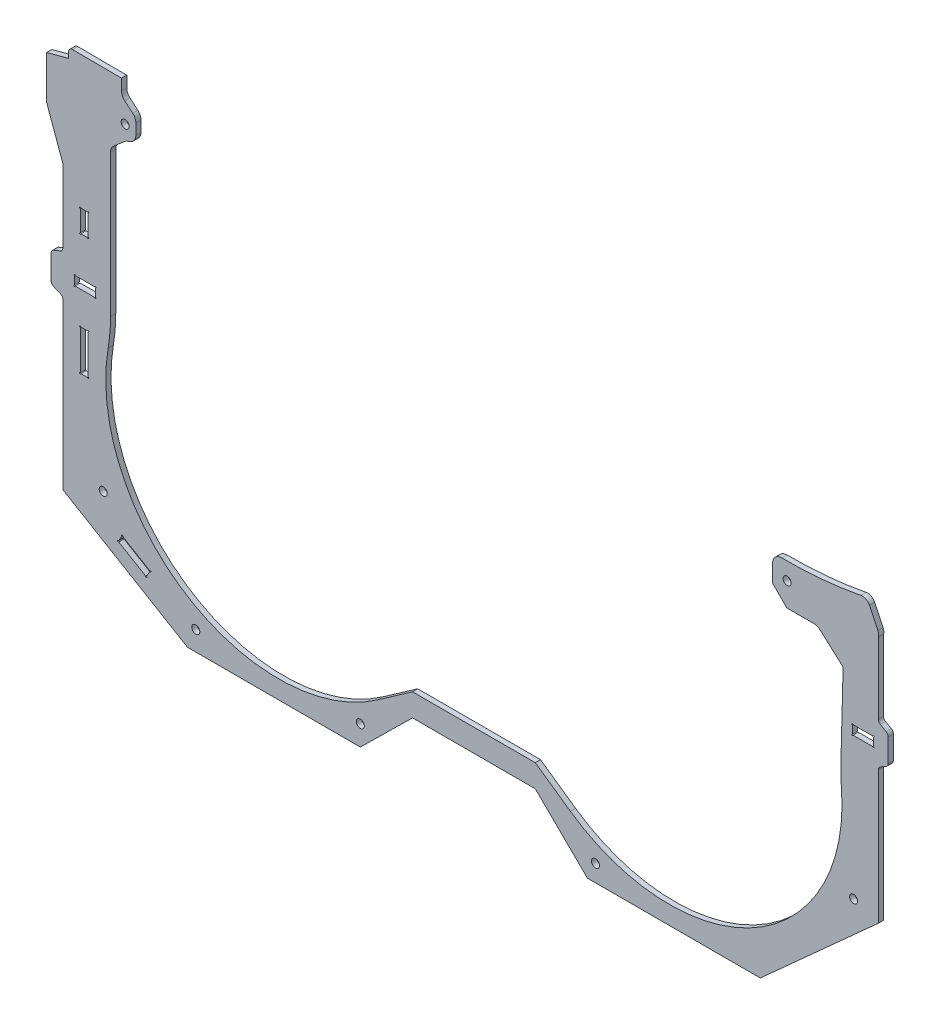
SolidWorks part; units mm, degrees
material "PPS"
ref_plane "前视基准面" through (0, 0, 0) normal (0, 0, 1) x (1, 0, 0)
ref_plane "上视基准面" through (0, 0, 0) normal (0, 1, 0) x (1, 0, 0)
ref_plane "右视基准面" through (0, 0, 0) normal (1, 0, 0) x (0, 0, -1)
sketch "草图1" plane through (0, 0, 0) normal (0, 0, 1) x (1, 0, 0)
  line L0 (-816.4831, 0) -> (39952.7477, 0) construction
  line L1 (0, 10.8762) -> (0, -592.6628) construction
  line L2 (0, 0) -> (206.9686, -284.8678) construction
  line L9 (155.1848, -135.6229) -> (109.8918, -176.4655)
  line L10 (109.8918, -176.4655) -> (43.5772, -176.4655)
  line L60 (-109.8918, -176.4655) -> (-43.5772, -176.4655)
  line L119 (-133.4625, -19.9819) -> (-139.4195, -25.1039)
  line L187 (152.75, -77.5) -> (145.75, -77.5) construction
  line L188 (152.75, -77.5) -> (152.75, -75) construction
  line L189 (145.75, -77.5) -> (145.75, -75) construction
  line L190 (152.75, -75) -> (145.75, -75) construction
  line L191 (-145.75, -75) -> (-152.75, -75) construction
  line L192 (-152.75, -75) -> (-152.75, -77.5) construction
  line L193 (-152.75, -77.5) -> (-145.75, -77.5) construction
  line L194 (-145.75, -77.5) -> (-145.75, -75) construction
  line L195 (145.25, -74.5) -> (153.25, -74.5)
  line L196 (153.25, -74.5) -> (153.25, -78)
  line L197 (153.25, -78) -> (145.25, -78)
  line L198 (145.25, -78) -> (145.25, -74.5)
  line L199 (-153.25, -78) -> (-145.25, -78)
  line L200 (-153.25, -74.5) -> (-153.25, -78)
  line L201 (-145.25, -74.5) -> (-153.25, -74.5)
  line L202 (-145.25, -78) -> (-145.25, -74.5)
  line L204 (-135.1929, 0) -> (-155.5041, 0.108)
  line L205 (-155.5041, 3.8169) -> (-155.5041, -3.6009) construction
  line L206 (-155.5041, 0.108) -> (-155.5041, -3.6009)
  line L207 (-155.5041, -3.6009) -> (-163.9299, -5.8429)
  line L208 (-155.5041, -3.6009) -> (-170.0041, -7.4592) construction
  line L209 (-163.9299, -5.8429) -> (-163.9299, -22.4613)
  line L210 (-163.9299, -22.4613) -> (-157.7253, -39.5836)
  line L211 (-157.7253, -39.5836) -> (-157.7253, -148.0115)
  line L212 (-157.7253, -148.0115) -> (-109.8918, -176.4655)
  line L215 (114.5778, -32.685) -> (114.5778, -42.9165)
  line L216 (120.0778, -48.4165) -> (131.782, -48.4165)
  line L217 (131.782, -48.4165) -> (141.6604, -57.2625)
  line L219 (151.7709, -31.6811) -> (155.0114, -38.4796)
  line L220 (155.1848, -40.6053) -> (155.1848, -135.6229)
  line L221 (120.1823, -39.335) -> (149.4323, -39.335) construction
  line L222 (91.0014, -48.4165) -> (142.5788, -48.4165) construction
  line L223 (75, -103.2286) -> (164.6276, -103.2286) construction
  line L224 (75, -103.2286) -> (37.0006, -157.4975) construction
  line L226 (37.0006, -157.4975) -> (23.5599, -148.0862)
  line L227 (23.5599, -148.0862) -> (-23.5599, -148.0862)
  line L228 (23.5599, -156.7643) -> (-23.5599, -156.7643)
  line L229 (23.5599, -156.7643) -> (43.5772, -176.4655)
  line L230 (-37.0006, -157.4975) -> (-23.5599, -148.0862)
  line L231 (-23.5599, -156.7643) -> (-43.5772, -176.4655)
  line L233 (114.5778, -42.9165) -> (120.0778, -48.4165)
  line L234 (75, -103.2286) -> (140.6832, -94.5813) construction
  line L235 (141.6604, -57.2625) -> (140.6832, -94.5813)
  line L236 (140.6832, -94.5813) -> (140.6832, -61.0285) construction
  line L238 (-139.4195, -87.7629) -> (-75, -103.2286) construction
  line L239 (-75, -103.2286) -> (-141.25, -103.2286) construction
  line L240 (-139.4195, -25.1039) -> (-139.4195, -87.7629)
  line L241 (-135.1929, 0) -> (-135.1929, -5.85)
  line L242 (-135.1929, -5.85) -> (-129.7197, -10.5767)
  line L243 (-129.7197, -10.5767) -> (-129.7197, -18.7984)
  line L244 (-129.7197, -18.7984) -> (-133.4625, -19.9819)
  circle A76 centre (75, -103.2286) radius 66.25 construction
  circle A78 centre (-133.8062, -14.6009) radius 1.55
  arc A79 (155.0114, -38.4796) -> (155.1848, -40.6053) centre (152.3033, -39.7704) cw
  circle A80 centre (-75, -103.2286) radius 66.25 construction
  arc A81 (148.5011, -30.0249) -> (151.7709, -31.6811) centre (149.0628, -32.9719) cw
  arc A82 (153.902, -42.309) -> (155.0114, -38.4796) centre (152.3033, -39.7704) ccw construction
  arc A83 (148.5011, -30.0249) -> (114.5778, -32.685) centre (119.5082, 122.0773) cw
  arc A84 (97.7907, -31.2329) -> (148.5011, -30.0249) centre (119.5082, 122.0773) ccw construction
  circle A85 centre (149.4323, -39.335) radius 1.55 construction
  circle A86 centre (120.1823, -39.335) radius 1.55
  arc A87 (37.0006, -157.4975) -> (141.25, -103.2286) centre (75, -103.2286) ccw
  arc A88 (-37.0006, -157.4975) -> (-141.25, -103.2286) centre (-75, -103.2286) cw
  arc A89 (140.6832, -94.5813) -> (141.25, -103.2286) centre (75, -103.2286) cw
  arc A91 (-141.25, -103.2286) -> (-139.4195, -87.7629) centre (-75, -103.2286) cw
  point P10 (149.25, -75)
  point P29 (0, -148.0862)
  point P38 (153.25, -76.25)
  point P92 (0, -156.7643)
  dimension "D1" = 36
  dimension "D2" = 75
  dimension "D3" = 132.5
  dimension "D6" = 75
  dimension "D7" = 149.25
  dimension "D15" = 125
  dimension "D14" = 3.1
  dimension "D4" = 2.5
  dimension "D5" = 7
  dimension "D8" = 7
  dimension "D9" = 0.5
  dimension "D10" = 0.5
  dimension "D11" = 0.5
  dimension "D12" = 0.5
  dimension "D13" = 29.25
  dimension "D16" = 7.5
  dimension "D17" = 1.5
  dimension "D18" = 13.5
extrude "凸台-拉伸1" add sketch "草图1" along normal blind 2
sketch "草图2" plane through (0, 0, 0) normal (0, 0, 1) x (1, 0, 0)
  line L0 (155.1848, -68.75) -> (158.9348, -70.9151)
  line L1 (155.1848, -135.6229) -> (155.1848, -40.6053) construction
  line L2 (158.9348, -70.9151) -> (158.9348, -81.5849)
  line L3 (158.9348, -81.5849) -> (155.1848, -83.75)
  line L4 (155.1848, -83.75) -> (155.1848, -68.75)
  line L5 (153.25, -76.25) -> (184.2947, -76.25) construction
  line L6 (153.25, -78) -> (153.25, -74.5) construction
  line L7 (-153.25, -76.25) -> (-171.2105, -76.25) construction
  line L8 (-153.25, -74.5) -> (-153.25, -78) construction
  line L9 (-157.7253, -68.75) -> (-157.7253, -83.75)
  line L10 (-157.7253, -39.5836) -> (-157.7253, -148.0115) construction
  line L11 (-157.7253, -83.75) -> (-162.2253, -81.886)
  line L12 (-162.2253, -81.886) -> (-162.2253, -70.614)
  line L13 (-162.2253, -70.614) -> (-157.7253, -68.75)
  dimension "D1" = 3.75
  dimension "D2" = 7.5
  dimension "D3" = 60
  dimension "D4" = 67.5
  dimension "D5" = 4.5
extrude "凸台-拉伸2" add sketch "草图2" against normal up to surface from surface up to face at (-132.2562, -14.6009, 0) starting at face at (149.25, -76.25, 2)
fillet "圆角1" radius 66.25 2 edges at (-139.4195, -87.7629, 1) (140.6832, -94.5813, 1)
fillet "圆角4" radius 1.5 9 edges at (155.1848, -68.75, 1) (158.9348, -70.9151, 1) (155.1848, -83.75, 1) (158.9348, -81.5849, 1) (-155.5041, 0.108, 1) (-157.7253, -68.75, 1) (-162.2253, -70.614, 1) (-162.2253, -81.886, 1) (-157.7253, -83.75, 1)
sketch "板状设备接口" plane through (0, 0, 2) normal (0, 0, 1) x (1, 0, 0)
  line L0 (-151, -90.5) -> (-148, -90.5)
  line L1 (-148, -90.5) -> (-148, -106)
  line L2 (-148, -106) -> (-151, -106)
  line L3 (-151, -106) -> (-151, -90.5)
  line L4 (-148, -77.5) -> (-148, -75) construction
  line L5 (-151, -75) -> (-151, -77.5) construction
  line L6 (-151, -51) -> (-148, -51)
  line L7 (-148, -51) -> (-148, -59.5)
  line L8 (-148, -59.5) -> (-151, -59.5)
  line L9 (-151, -59.5) -> (-151, -51)
  line L10 (-145.25, -74.5) -> (-153.25, -74.5) construction
  line L11 (-153.25, -78) -> (-145.25, -78) construction
  line L12 (-134.9623, -151.9529) -> (-124.2193, -158.3434)
  line L13 (-124.2193, -158.3434) -> (-125.753, -160.9217)
  line L14 (-125.753, -160.9217) -> (-136.496, -154.5312)
  line L15 (-136.496, -154.5312) -> (-134.9623, -151.9529)
  line L21 (-157.7253, -148.0115) -> (-109.8918, -176.4655) construction
  line L22 (-131.1245, -157.7265) -> (-133.8085, -162.2385) construction
  dimension "D1" = 15
  dimension "D2" = 8.5
  dimension "D3" = 12.5
  dimension "D4" = 15.5
  dimension "D5" = 5.25
  dimension "D6" = 12.5
  dimension "D7" = 3
extrude "设备接口" cut sketch "板状设备接口" against normal through all
sketch "草图4" plane through (0, 0, 0) normal (0, 0, 1) x (1, 0, 0)
  line L0 (-157.7253, -84.7523) -> (-157.7253, -148.0115) construction
  line L1 (-109.8918, -176.4655) -> (-43.5772, -176.4655) construction
  line L2 (155.1848, -135.6229) -> (155.1848, -84.616) construction
  line L3 (-43.5772, -168.7155) -> (-43.5772, -176.4655) construction
  line L4 (43.5772, -176.4655) -> (109.8918, -176.4655) construction
  circle A0 centre (-142.2253, -140.8215) radius 1.55
  circle A1 centre (-43.5772, -168.7155) radius 1.55
  circle A2 centre (-106.713, -168.9655) radius 1.55
  circle A3 centre (46.656, -169.9655) radius 1.55
  circle A4 centre (145.6848, -132.301) radius 1.55
  dimension "D5" = 3.1
  dimension "D1" = 15.5
  dimension "D2" = 7.5
  dimension "D3" = 7.75
  dimension "D4" = 9.5
  dimension "D6" = 6.5
extrude "切除-拉伸3" cut sketch "草图4" along normal through all
fillet "圆角5" radius 3.5 7 edges at (131.782, -48.4165, 1) (114.5778, -32.685, 1) (-139.4195, -25.1039, 1) (-129.7197, -10.5767, 1) (-135.1929, -5.85, 1) (-133.4625, -19.9819, 1) (-129.7197, -18.7984, 1)
sketch "过切除" plane through (0, 0, 0) normal (0, 0, 1) x (1, 0, 0)
  circle A0 centre (-151, -51) radius 0.25
  circle A1 centre (-148, -51) radius 0.25
  circle A2 centre (-151, -59.5) radius 0.25
  circle A3 centre (-148, -59.5) radius 0.25
  circle A4 centre (-153.25, -74.5) radius 0.25
  circle A5 centre (-145.25, -74.5) radius 0.25
  circle A6 centre (-145.25, -78) radius 0.25
  circle A7 centre (-153.25, -78) radius 0.25
  circle A8 centre (-151, -90.5) radius 0.25
  circle A9 centre (-148, -90.5) radius 0.25
  circle A10 centre (-151, -106) radius 0.25
  circle A11 centre (-148, -106) radius 0.25
  circle A12 centre (-134.9623, -151.9529) radius 0.25
  circle A13 centre (-136.496, -154.5312) radius 0.25
  circle A14 centre (-124.2193, -158.3434) radius 0.25
  circle A15 centre (-125.753, -160.9217) radius 0.25
  circle A16 centre (145.25, -74.5) radius 0.25
  circle A17 centre (153.25, -74.5) radius 0.25
  circle A18 centre (153.25, -78) radius 0.25
  circle A19 centre (145.25, -78) radius 0.25
  dimension "D1" = 0.5
extrude "这个是因为刀的限制不能切直角" cut sketch "过切除" along normal through all
